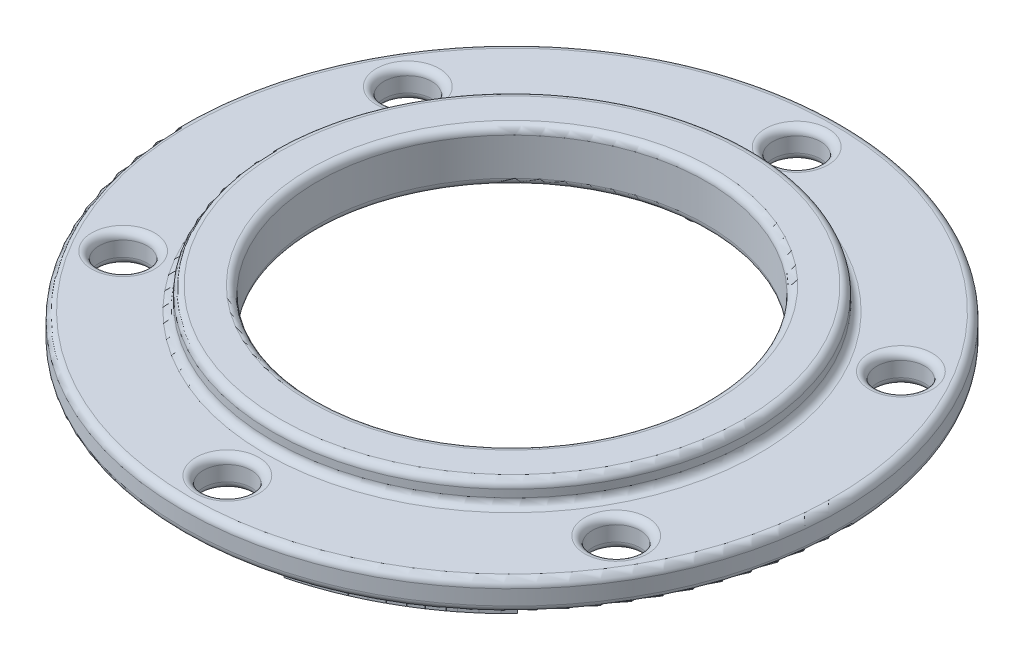
SolidWorks part; units mm, degrees
note: '?' marks a value the reader was unsure of.
other "graphite_1"
other "blue_5"
other "blue_8"
other "white_9"
other "white_3"
other "white_5"
other "white_10"
other "white_6"
other "white_2"
other "white_7"
other "white_8"
other "white"
other "white_4"
other "blue_6"
other "blue_4"
other "blue_2"
other "blue_1"
other "blue_3"
other "blue_7"
ref_plane "Front Plane" through (0, 0, 0) normal (0, 0, 1) x (1, 0, 0)
ref_plane "Top Plane" through (0, 0, 0) normal (0, 1, 0) x (1, 0, 0)
ref_plane "Right Plane" through (0, 0, 0) normal (1, 0, 0) x (0, 0, -1)
sketch "Sketch1" plane through (0, 0, 0) normal (0, 1, 0) x (1, 0, 0)
  circle A0 centre (0, 0) radius 22.025
  arc A1 (-0.6528, -22.0153) -> (-0.6528, 22.0153) centre (0, 0) ccw construction
  circle A2 centre (0, 19.025) radius 1.6
  circle A3 centre (16.4761, 9.5125) radius 1.6
  circle A4 centre (16.4761, -9.5125) radius 1.6
  circle A5 centre (0, -19.025) radius 1.6
  circle A6 centre (-16.4761, -9.5125) radius 1.6
  circle A7 centre (-16.4761, 9.5125) radius 1.6
  circle A8 centre (0, 0) radius 13
  point P21 (0, 0)
  dimension "D1" = 3.2
  dimension "D3" = 26
  dimension "D4" = 44.05
  dimension "D2" = 6
extrude "Boss-Extrude1" add sketch "Sketch1" against normal blind 2
ref_axis "Axis1" through (0, -2.805, 0) along (0, 1, 0)?
sketch "Sketch2" plane through (0, 0, 0) normal (0, 1, 0) x (1, 0, 0)
  circle A0 centre (0, 0) radius 13
  circle A1 centre (0, 0) radius 16
  dimension "D1" = 26
  dimension "D2" = 32
extrude "Boss-Extrude2" add sketch "Sketch2" along normal blind 1.5
fillet "Fillet1" radius 0.5 18 edges at (0, 0, 22.025) (0, 0, -17.425) (16.4761, 0, -7.9125) (16.4761, 0, 11.1125) (0, 0, 20.625) (-16.4761, 0, 11.1125) (-16.4761, 0, -7.9125) (0, -2, 22.025) (0, -2, -17.425) (0, -2, 13) (16.4761, -2, -7.9125) (16.4761, -2, 11.1125) (0, -2, 20.625) (-16.4761, -2, 11.1125) (-16.4761, -2, -7.9125) (0, 0, 16) (0, 1.5, 13) (0, 1.5, 16)
sketch "GL_free_blue" plane through (0, 0, 0) normal (0, 1, 0) x (1, 0, 0)
  line L0 (9.3065, -18.9293) -> (8.4044, -19.3469)
  line L1 (8.4044, -19.3469) -> (7.0284, -16.9635)
  line L2 (7.0284, -16.9635) -> (7.8857, -16.4685)
  line L3 (7.8857, -16.4685) -> (9.3065, -18.9293)
  line L4 (10.1151, -18.5099) -> (8.0238, -14.8877)
  line L5 (8.0238, -14.8877) -> (8.8812, -14.3927)
  line L6 (8.8812, -14.3927) -> (10.9726, -18.015)
  line L7 (10.9726, -18.015) -> (10.1151, -18.5099)
  line L8 (10.3193, -15.0635) -> (11.1766, -14.5685)
  line L9 (11.1766, -14.5685) -> (12.5533, -16.953)
  line L10 (12.5533, -16.953) -> (11.7407, -17.5254)
  line L11 (11.7407, -17.5254) -> (10.3193, -15.0635)
  line L12 (-11.4547, -8.409) -> (-9.9656, -11.4327)
  line L13 (-9.9656, -11.4327) -> (-9.316, -14.6968)
  line L14 (-9.316, -14.6968) -> (-10.4966, -16.447)
  line L15 (-10.4966, -16.447) -> (-10.5417, -16.3435)
  line L16 (-10.5417, -16.3435) -> (-10.6348, -16.204)
  line L17 (-10.6348, -16.204) -> (-10.8207, -16.0356)
  line L18 (-10.8207, -16.0356) -> (-11.0474, -15.9284)
  line L19 (-11.0474, -15.9284) -> (-11.2118, -15.8957)
  line L20 (-11.2118, -15.8957) -> (-11.3172, -15.8933)
  line L21 (-11.3172, -15.8933) -> (-10.3675, -14.4853)
  line L22 (-10.3675, -14.4853) -> (-10.9112, -11.7534)
  line L23 (-10.9112, -11.7534) -> (-12.3304, -8.8719)
  line L24 (-12.3304, -8.8719) -> (-13.9598, -5.9918)
  line L25 (-13.9598, -5.9918) -> (-13.0981, -5.5043)
  line L26 (-13.0981, -5.5043) -> (-11.4547, -8.409)
  line L27 (19.1817, 0.2481) -> (19.145, 0.0001)
  line L28 (19.145, 0.0001) -> (19.1614, -0.1668)
  line L29 (19.1614, -0.1668) -> (19.2101, -0.3273)
  line L30 (19.2101, -0.3273) -> (19.3053, -0.495)
  line L31 (19.3053, -0.495) -> (17.577, -0.495)
  line L32 (17.577, -0.495) -> (15.272, -2.385)
  line L33 (15.272, -2.385) -> (14.5924, -4.2302)
  line L34 (14.5924, -4.2302) -> (13.4188, -7.1349)
  line L35 (13.4188, -7.1349) -> (11.6421, -9.7689)
  line L36 (11.6421, -9.7689) -> (9.8494, -11.5002)
  line L37 (9.8494, -11.5002) -> (9.794, -11.2758)
  line L38 (9.794, -11.2758) -> (9.7196, -11.1365)
  line L39 (9.7196, -11.1365) -> (9.6194, -11.0144)
  line L40 (9.6194, -11.0144) -> (9.4298, -10.8738)
  line L41 (9.4298, -10.8738) -> (9.2839, -10.8134)
  line L42 (9.2839, -10.8134) -> (9.1617, -10.788)
  line L43 (9.1617, -10.788) -> (10.8796, -9.129)
  line L44 (10.8796, -9.129) -> (12.5399, -6.6676)
  line L45 (12.5399, -6.6676) -> (13.6687, -3.8736)
  line L46 (13.6687, -3.8736) -> (14.4361, -1.7902)
  line L47 (14.4361, -1.7902) -> (17.223, 0.495)
  line L48 (17.223, 0.495) -> (19.3047, 0.495)
  line L49 (19.3047, 0.495) -> (19.2459, 0.403)
  line L50 (19.2459, 0.403) -> (19.1817, 0.2481)
  line L51 (-17.6255, 0.445) -> (-17.105, 0.445)
  line L52 (-17.105, 0.445) -> (-17.105, -0.445)
  line L53 (-17.105, -0.445) -> (-17.6255, -0.445)
  line L54 (-17.6255, -0.445) -> (-17.6255, -1.4051)
  line L55 (-17.6255, -1.4051) -> (-17.0578, -1.3454)
  line L56 (-17.0578, -1.3454) -> (-16.9648, -2.2305)
  line L57 (-16.9648, -2.2305) -> (-17.6255, -2.3)
  line L58 (-17.6255, -2.3) -> (-17.6255, -3.1586)
  line L59 (-17.6255, -3.1586) -> (-17.3907, -4.7392)
  line L60 (-17.3907, -4.7392) -> (-17.4793, -4.6944)
  line L61 (-17.4793, -4.6944) -> (-17.6302, -4.6486)
  line L62 (-17.6302, -4.6486) -> (-17.7873, -4.6331)
  line L63 (-17.7873, -4.6331) -> (-17.9444, -4.6486)
  line L64 (-17.9444, -4.6486) -> (-18.1667, -4.7281)
  line L65 (-18.1667, -4.7281) -> (-18.2979, -4.8158)
  line L66 (-18.2979, -4.8158) -> (-18.3699, -4.8847)
  line L67 (-18.3699, -4.8847) -> (-18.6155, -3.2317)
  line L68 (-18.6155, -3.2317) -> (-18.6155, -2.404)
  line L69 (-18.6155, -2.404) -> (-19.5406, -2.5013)
  line L70 (-19.5406, -2.5013) -> (-19.6336, -1.6161)
  line L71 (-19.6336, -1.6161) -> (-18.6155, -1.5091)
  line L72 (-18.6155, -1.5091) -> (-18.6155, -0.445)
  line L73 (-18.6155, -0.445) -> (-19.695, -0.445)
  line L74 (-19.695, -0.445) -> (-19.695, 0.445)
  line L75 (-19.695, 0.445) -> (-18.6155, 0.445)
  line L76 (-18.6155, 0.445) -> (-18.6155, 1.5091)
  line L77 (-18.6155, 1.5091) -> (-19.6336, 1.6161)
  line L78 (-19.6336, 1.6161) -> (-19.5406, 2.5013)
  line L79 (-19.5406, 2.5013) -> (-18.6155, 2.404)
  line L80 (-18.6155, 2.404) -> (-18.6155, 3.2317)
  line L81 (-18.6155, 3.2317) -> (-18.3699, 4.8847)
  line L82 (-18.3699, 4.8847) -> (-18.2979, 4.8158)
  line L83 (-18.2979, 4.8158) -> (-18.1667, 4.7281)
  line L84 (-18.1667, 4.7281) -> (-17.9444, 4.6486)
  line L85 (-17.9444, 4.6486) -> (-17.7873, 4.6331)
  line L86 (-17.7873, 4.6331) -> (-17.6302, 4.6486)
  line L87 (-17.6302, 4.6486) -> (-17.4793, 4.6944)
  line L88 (-17.4793, 4.6944) -> (-17.3907, 4.7392)
  line L89 (-17.3907, 4.7392) -> (-17.6255, 3.1586)
  line L90 (-17.6255, 3.1586) -> (-17.6255, 2.3)
  line L91 (-17.6255, 2.3) -> (-16.9648, 2.2305)
  line L92 (-16.9648, 2.2305) -> (-17.0578, 1.3454)
  line L93 (-17.0578, 1.3454) -> (-17.6255, 1.4051)
  line L94 (-17.6255, 1.4051) -> (-17.6255, 0.445)
  line L95 (-2.8163, 14.7905) -> (-2.8509, 14.5569)
  line L96 (-2.8509, 14.5569) -> (-2.8162, 14.3232)
  line L97 (-2.8162, 14.3232) -> (-2.7153, 14.1098)
  line L98 (-2.7153, 14.1098) -> (-2.6151, 13.9877)
  line L99 (-2.6151, 13.9877) -> (-2.5403, 13.9235)
  line L100 (-2.5403, 13.9235) -> (-4.9445, 13.3241)
  line L101 (-4.9445, 13.3241) -> (-6.7566, 13.1559)
  line L102 (-6.7566, 13.1559) -> (-9.208, 14.3636)
  line L103 (-9.208, 14.3636) -> (-10.1607, 15.9492)
  line L104 (-10.1607, 15.9492) -> (-10.0109, 15.9496)
  line L105 (-10.0109, 15.9496) -> (-9.8464, 15.9823)
  line L106 (-9.8464, 15.9823) -> (-9.6197, 16.0895)
  line L107 (-9.6197, 16.0895) -> (-9.4338, 16.258)
  line L108 (-9.4338, 16.258) -> (-9.3123, 16.4594)
  line L109 (-9.3123, 16.4594) -> (-8.5093, 15.123)
  line L110 (-8.5093, 15.123) -> (-6.5698, 14.1675)
  line L111 (-6.5698, 14.1675) -> (-5.1109, 14.3029)
  line L112 (-5.1109, 14.3029) -> (-2.7798, 14.8841)
  line L113 (-2.7798, 14.8841) -> (-2.8163, 14.7905)
  line L114 (10.8629, 13.5214) -> (10.6712, 13.512)
  line L115 (10.6712, 13.512) -> (10.5482, 13.4747)
  line L116 (10.5482, 13.4747) -> (10.4348, 13.4141)
  line L117 (10.4348, 13.4141) -> (10.2924, 13.2851)
  line L118 (10.2924, 13.2851) -> (10.1897, 13.1033)
  line L119 (10.1897, 13.1033) -> (9.5768, 14.8192)
  line L120 (9.5768, 14.8192) -> (9.4533, 16.4797)
  line L121 (9.4533, 16.4797) -> (9.6662, 16.377)
  line L122 (9.6662, 16.377) -> (9.8211, 16.3462)
  line L123 (9.8211, 16.3462) -> (9.979, 16.3462)
  line L124 (9.979, 16.3462) -> (10.208, 16.4035)
  line L125 (10.208, 16.4035) -> (10.3472, 16.4779)
  line L126 (10.3472, 16.4779) -> (10.4406, 16.5529)
  line L127 (10.4406, 16.5529) -> (10.5541, 15.0261)
  line L128 (10.5541, 15.0261) -> (11.1218, 13.4371)
  line L129 (11.1218, 13.4371) -> (10.989, 13.4964)
  line L130 (10.989, 13.4964) -> (10.8629, 13.5214)
extrude "GL_free_blue_raised" add sketch "GL_free_blue" along normal blind 0.6 from offset 2.6 separate body
sketch "GL_free_white" plane through (0, 0, 0) normal (0, 1, 0) x (1, 0, 0)
  line L0 (-10.6982, -17.344) -> (-10.8263, -17.4491)
  line L1 (-10.8263, -17.4491) -> (-10.9723, -17.5272)
  line L2 (-10.9723, -17.5272) -> (-11.1309, -17.5753)
  line L3 (-11.1309, -17.5753) -> (-11.2957, -17.5915)
  line L4 (-11.2957, -17.5915) -> (-11.4605, -17.5753)
  line L5 (-11.4605, -17.5753) -> (-11.6191, -17.5272)
  line L6 (-11.6191, -17.5272) -> (-11.7651, -17.4491)
  line L7 (-11.7651, -17.4491) -> (-11.8932, -17.344)
  line L8 (-11.8932, -17.344) -> (-11.9983, -17.216)
  line L9 (-11.9983, -17.216) -> (-12.0764, -17.0699)
  line L10 (-12.0764, -17.0699) -> (-12.1244, -16.9114)
  line L11 (-12.1244, -16.9114) -> (-12.1407, -16.7466)
  line L12 (-12.1407, -16.7466) -> (-12.1244, -16.5817)
  line L13 (-12.1244, -16.5817) -> (-12.0764, -16.4232)
  line L14 (-12.0764, -16.4232) -> (-11.9983, -16.2771)
  line L15 (-11.9983, -16.2771) -> (-11.8932, -16.1491)
  line L16 (-11.8932, -16.1491) -> (-11.7651, -16.044)
  line L17 (-11.7651, -16.044) -> (-11.6191, -15.9659)
  line L18 (-11.6191, -15.9659) -> (-11.4605, -15.9178)
  line L19 (-11.4605, -15.9178) -> (-11.2957, -15.9016)
  line L20 (-11.2957, -15.9016) -> (-11.1309, -15.9178)
  line L21 (-11.1309, -15.9178) -> (-10.9723, -15.9659)
  line L22 (-10.9723, -15.9659) -> (-10.8263, -16.044)
  line L23 (-10.8263, -16.044) -> (-10.6982, -16.1491)
  line L24 (-10.6982, -16.1491) -> (-10.5931, -16.2771)
  line L25 (-10.5931, -16.2771) -> (-10.515, -16.4232)
  line L26 (-10.515, -16.4232) -> (-10.467, -16.5817)
  line L27 (-10.467, -16.5817) -> (-10.4507, -16.7466)
  line L28 (-10.4507, -16.7466) -> (-10.467, -16.9114)
  line L29 (-10.467, -16.9114) -> (-10.515, -17.0699)
  line L30 (-10.515, -17.0699) -> (-10.5931, -17.216)
  line L31 (-10.5931, -17.216) -> (-10.6982, -17.344)
  line L32 (11.7323, -17.531) -> (10.9811, -18.0098)
  line L33 (10.9811, -18.0098) -> (8.8848, -14.379)
  line L34 (8.8848, -14.379) -> (8.0102, -14.884)
  line L35 (8.0102, -14.884) -> (10.1063, -18.5147)
  line L36 (10.1063, -18.5147) -> (9.3155, -18.9249)
  line L37 (9.3155, -18.9249) -> (7.8894, -16.4548)
  line L38 (7.8894, -16.4548) -> (7.0147, -16.9598)
  line L39 (7.0147, -16.9598) -> (8.3952, -19.3509)
  line L40 (8.3952, -19.3509) -> (7.592, -19.6815)
  line L41 (7.592, -19.6815) -> (6.6171, -20.0303)
  line L42 (6.6171, -20.0303) -> (6.1236, -20.1866)
  line L43 (6.1236, -20.1866) -> (5.2036, -20.4422)
  line L44 (5.2036, -20.4422) -> (4.4572, -16.6159)
  line L45 (4.4572, -16.6159) -> (7.9525, -13.7742)
  line L46 (7.9525, -13.7742) -> (12.1612, -12.168)
  line L47 (12.1612, -12.168) -> (15.1011, -14.727)
  line L48 (15.1011, -14.727) -> (14.5459, -15.278)
  line L49 (14.5459, -15.278) -> (13.7787, -15.9733)
  line L50 (13.7787, -15.9733) -> (12.9783, -16.6302)
  line L51 (12.9783, -16.6302) -> (12.5614, -16.947)
  line L52 (12.5614, -16.947) -> (11.1803, -14.5548)
  line L53 (11.1803, -14.5548) -> (10.3056, -15.0598)
  line L54 (10.3056, -15.0598) -> (11.7323, -17.531)
  line L55 (9.6124, -12.1459) -> (9.4919, -12.2448)
  line L56 (9.4919, -12.2448) -> (9.3544, -12.3182)
  line L57 (9.3544, -12.3182) -> (9.2053, -12.3635)
  line L58 (9.2053, -12.3635) -> (9.0502, -12.3787)
  line L59 (9.0502, -12.3787) -> (8.8951, -12.3635)
  line L60 (8.8951, -12.3635) -> (8.746, -12.3182)
  line L61 (8.746, -12.3182) -> (8.6086, -12.2448)
  line L62 (8.6086, -12.2448) -> (8.4881, -12.1459)
  line L63 (8.4881, -12.1459) -> (8.3892, -12.0254)
  line L64 (8.3892, -12.0254) -> (8.3158, -11.888)
  line L65 (8.3158, -11.888) -> (8.2705, -11.7389)
  line L66 (8.2705, -11.7389) -> (8.2552, -11.5838)
  line L67 (8.2552, -11.5838) -> (8.2705, -11.4287)
  line L68 (8.2705, -11.4287) -> (8.3158, -11.2795)
  line L69 (8.3158, -11.2795) -> (8.3892, -11.1421)
  line L70 (8.3892, -11.1421) -> (8.4881, -11.0216)
  line L71 (8.4881, -11.0216) -> (8.6086, -10.9228)
  line L72 (8.6086, -10.9228) -> (8.746, -10.8493)
  line L73 (8.746, -10.8493) -> (8.8951, -10.8041)
  line L74 (8.8951, -10.8041) -> (9.0502, -10.7888)
  line L75 (9.0502, -10.7888) -> (9.2053, -10.8041)
  line L76 (9.2053, -10.8041) -> (9.3544, -10.8493)
  line L77 (9.3544, -10.8493) -> (9.4919, -10.9228)
  line L78 (9.4919, -10.9228) -> (9.6124, -11.0216)
  line L79 (9.6124, -11.0216) -> (9.7112, -11.1421)
  line L80 (9.7112, -11.1421) -> (9.7847, -11.2795)
  line L81 (9.7847, -11.2795) -> (9.8299, -11.4287)
  line L82 (9.8299, -11.4287) -> (9.8452, -11.5838)
  line L83 (9.8452, -11.5838) -> (9.8299, -11.7389)
  line L84 (9.8299, -11.7389) -> (9.7847, -11.888)
  line L85 (9.7847, -11.888) -> (9.7112, -12.0254)
  line L86 (9.7112, -12.0254) -> (9.6124, -12.1459)
  line L87 (-17.3456, -6.0991) -> (-17.483, -6.1726)
  line L88 (-17.483, -6.1726) -> (-17.6322, -6.2178)
  line L89 (-17.6322, -6.2178) -> (-17.7873, -6.2331)
  line L90 (-17.7873, -6.2331) -> (-17.9424, -6.2178)
  line L91 (-17.9424, -6.2178) -> (-18.0915, -6.1726)
  line L92 (-18.0915, -6.1726) -> (-18.2289, -6.0991)
  line L93 (-18.2289, -6.0991) -> (-18.3494, -6.0002)
  line L94 (-18.3494, -6.0002) -> (-18.4483, -5.8798)
  line L95 (-18.4483, -5.8798) -> (-18.5217, -5.7423)
  line L96 (-18.5217, -5.7423) -> (-18.567, -5.5932)
  line L97 (-18.567, -5.5932) -> (-18.5822, -5.4381)
  line L98 (-18.5822, -5.4381) -> (-18.567, -5.283)
  line L99 (-18.567, -5.283) -> (-18.5217, -5.1339)
  line L100 (-18.5217, -5.1339) -> (-18.4483, -4.9964)
  line L101 (-18.4483, -4.9964) -> (-18.3494, -4.876)
  line L102 (-18.3494, -4.876) -> (-18.2289, -4.7771)
  line L103 (-18.2289, -4.7771) -> (-18.0915, -4.7037)
  line L104 (-18.0915, -4.7037) -> (-17.9424, -4.6584)
  line L105 (-17.9424, -4.6584) -> (-17.7873, -4.6431)
  line L106 (-17.7873, -4.6431) -> (-17.6322, -4.6584)
  line L107 (-17.6322, -4.6584) -> (-17.483, -4.7037)
  line L108 (-17.483, -4.7037) -> (-17.3456, -4.7771)
  line L109 (-17.3456, -4.7771) -> (-17.2251, -4.876)
  line L110 (-17.2251, -4.876) -> (-17.1263, -4.9964)
  line L111 (-17.1263, -4.9964) -> (-17.0528, -5.1339)
  line L112 (-17.0528, -5.1339) -> (-17.0076, -5.283)
  line L113 (-17.0076, -5.283) -> (-16.9923, -5.4381)
  line L114 (-16.9923, -5.4381) -> (-17.0076, -5.5932)
  line L115 (-17.0076, -5.5932) -> (-17.0528, -5.7423)
  line L116 (-17.0528, -5.7423) -> (-17.1263, -5.8798)
  line L117 (-17.1263, -5.8798) -> (-17.2251, -6.0002)
  line L118 (-17.2251, -6.0002) -> (-17.3456, -6.0991)
  line L119 (20.4694, -0.7026) -> (20.3234, -0.7807)
  line L120 (20.3234, -0.7807) -> (20.1648, -0.8287)
  line L121 (20.1648, -0.8287) -> (20, -0.845)
  line L122 (20, -0.845) -> (19.8352, -0.8287)
  line L123 (19.8352, -0.8287) -> (19.6766, -0.7807)
  line L124 (19.6766, -0.7807) -> (19.5306, -0.7026)
  line L125 (19.5306, -0.7026) -> (19.4025, -0.5975)
  line L126 (19.4025, -0.5975) -> (19.2974, -0.4694)
  line L127 (19.2974, -0.4694) -> (19.2193, -0.3234)
  line L128 (19.2193, -0.3234) -> (19.1713, -0.1648)
  line L129 (19.1713, -0.1648) -> (19.155, 0)
  line L130 (19.155, 0) -> (19.1713, 0.1648)
  line L131 (19.1713, 0.1648) -> (19.2193, 0.3234)
  line L132 (19.2193, 0.3234) -> (19.2974, 0.4694)
  line L133 (19.2974, 0.4694) -> (19.4025, 0.5975)
  line L134 (19.4025, 0.5975) -> (19.5306, 0.7026)
  line L135 (19.5306, 0.7026) -> (19.6766, 0.7807)
  line L136 (19.6766, 0.7807) -> (19.8352, 0.8287)
  line L137 (19.8352, 0.8287) -> (20, 0.845)
  line L138 (20, 0.845) -> (20.1648, 0.8287)
  line L139 (20.1648, 0.8287) -> (20.3234, 0.7807)
  line L140 (20.3234, 0.7807) -> (20.4694, 0.7026)
  line L141 (20.4694, 0.7026) -> (20.5975, 0.5975)
  line L142 (20.5975, 0.5975) -> (20.7026, 0.4694)
  line L143 (20.7026, 0.4694) -> (20.7807, 0.3234)
  line L144 (20.7807, 0.3234) -> (20.8287, 0.1648)
  line L145 (20.8287, 0.1648) -> (20.845, 0)
  line L146 (20.845, 0) -> (20.8287, -0.1648)
  line L147 (20.8287, -0.1648) -> (20.7807, -0.3234)
  line L148 (20.7807, -0.3234) -> (20.7026, -0.4694)
  line L149 (20.7026, -0.4694) -> (20.5975, -0.5975)
  line L150 (20.5975, -0.5975) -> (20.4694, -0.7026)
  line L151 (-17.2251, 4.876) -> (-17.3456, 4.7771)
  line L152 (-17.3456, 4.7771) -> (-17.483, 4.7037)
  line L153 (-17.483, 4.7037) -> (-17.6322, 4.6584)
  line L154 (-17.6322, 4.6584) -> (-17.7873, 4.6431)
  line L155 (-17.7873, 4.6431) -> (-17.9424, 4.6584)
  line L156 (-17.9424, 4.6584) -> (-18.0915, 4.7037)
  line L157 (-18.0915, 4.7037) -> (-18.2289, 4.7771)
  line L158 (-18.2289, 4.7771) -> (-18.3494, 4.876)
  line L159 (-18.3494, 4.876) -> (-18.4483, 4.9964)
  line L160 (-18.4483, 4.9964) -> (-18.5217, 5.1339)
  line L161 (-18.5217, 5.1339) -> (-18.567, 5.283)
  line L162 (-18.567, 5.283) -> (-18.5822, 5.4381)
  line L163 (-18.5822, 5.4381) -> (-18.567, 5.5932)
  line L164 (-18.567, 5.5932) -> (-18.5217, 5.7423)
  line L165 (-18.5217, 5.7423) -> (-18.4483, 5.8798)
  line L166 (-18.4483, 5.8798) -> (-18.3494, 6.0002)
  line L167 (-18.3494, 6.0002) -> (-18.2289, 6.0991)
  line L168 (-18.2289, 6.0991) -> (-18.0915, 6.1726)
  line L169 (-18.0915, 6.1726) -> (-17.9424, 6.2178)
  line L170 (-17.9424, 6.2178) -> (-17.7873, 6.2331)
  line L171 (-17.7873, 6.2331) -> (-17.6322, 6.2178)
  line L172 (-17.6322, 6.2178) -> (-17.483, 6.1726)
  line L173 (-17.483, 6.1726) -> (-17.3456, 6.0991)
  line L174 (-17.3456, 6.0991) -> (-17.2251, 6.0002)
  line L175 (-17.2251, 6.0002) -> (-17.1263, 5.8798)
  line L176 (-17.1263, 5.8798) -> (-17.0528, 5.7423)
  line L177 (-17.0528, 5.7423) -> (-17.0076, 5.5932)
  line L178 (-17.0076, 5.5932) -> (-16.9923, 5.4381)
  line L179 (-16.9923, 5.4381) -> (-17.0076, 5.283)
  line L180 (-17.0076, 5.283) -> (-17.0528, 5.1339)
  line L181 (-17.0528, 5.1339) -> (-17.1263, 4.9964)
  line L182 (-17.1263, 4.9964) -> (-17.2251, 4.876)
  line L183 (11.2549, 12.4135) -> (11.1572, 12.3333)
  line L184 (11.1572, 12.3333) -> (11.0457, 12.2737)
  line L185 (11.0457, 12.2737) -> (10.9247, 12.237)
  line L186 (10.9247, 12.237) -> (10.7988, 12.2246)
  line L187 (10.7988, 12.2246) -> (10.673, 12.237)
  line L188 (10.673, 12.237) -> (10.552, 12.2737)
  line L189 (10.552, 12.2737) -> (10.4405, 12.3333)
  line L190 (10.4405, 12.3333) -> (10.3428, 12.4135)
  line L191 (10.3428, 12.4135) -> (10.2626, 12.5112)
  line L192 (10.2626, 12.5112) -> (10.203, 12.6227)
  line L193 (10.203, 12.6227) -> (10.1662, 12.7437)
  line L194 (10.1662, 12.7437) -> (10.1539, 12.8695)
  line L195 (10.1539, 12.8695) -> (10.1662, 12.9954)
  line L196 (10.1662, 12.9954) -> (10.203, 13.1164)
  line L197 (10.203, 13.1164) -> (10.2626, 13.2279)
  line L198 (10.2626, 13.2279) -> (10.3428, 13.3256)
  line L199 (10.3428, 13.3256) -> (10.4405, 13.4058)
  line L200 (10.4405, 13.4058) -> (10.552, 13.4654)
  line L201 (10.552, 13.4654) -> (10.673, 13.5021)
  line L202 (10.673, 13.5021) -> (10.7988, 13.5145)
  line L203 (10.7988, 13.5145) -> (10.9247, 13.5021)
  line L204 (10.9247, 13.5021) -> (11.0457, 13.4654)
  line L205 (11.0457, 13.4654) -> (11.1572, 13.4058)
  line L206 (11.1572, 13.4058) -> (11.2549, 13.3256)
  line L207 (11.2549, 13.3256) -> (11.3351, 13.2279)
  line L208 (11.3351, 13.2279) -> (11.3947, 13.1164)
  line L209 (11.3947, 13.1164) -> (11.4314, 12.9954)
  line L210 (11.4314, 12.9954) -> (11.4438, 12.8695)
  line L211 (11.4438, 12.8695) -> (11.4314, 12.7437)
  line L212 (11.4314, 12.7437) -> (11.3947, 12.6227)
  line L213 (11.3947, 12.6227) -> (11.3351, 12.5112)
  line L214 (11.3351, 12.5112) -> (11.2549, 12.4135)
  line L215 (-1.4837, 13.9948) -> (-1.6042, 13.8959)
  line L216 (-1.6042, 13.8959) -> (-1.7416, 13.8225)
  line L217 (-1.7416, 13.8225) -> (-1.8908, 13.7772)
  line L218 (-1.8908, 13.7772) -> (-2.0458, 13.762)
  line L219 (-2.0458, 13.762) -> (-2.2009, 13.7772)
  line L220 (-2.2009, 13.7772) -> (-2.3501, 13.8225)
  line L221 (-2.3501, 13.8225) -> (-2.4875, 13.8959)
  line L222 (-2.4875, 13.8959) -> (-2.608, 13.9948)
  line L223 (-2.608, 13.9948) -> (-2.7068, 14.1153)
  line L224 (-2.7068, 14.1153) -> (-2.7803, 14.2527)
  line L225 (-2.7803, 14.2527) -> (-2.8255, 14.4018)
  line L226 (-2.8255, 14.4018) -> (-2.8408, 14.5569)
  line L227 (-2.8408, 14.5569) -> (-2.8255, 14.712)
  line L228 (-2.8255, 14.712) -> (-2.7803, 14.8612)
  line L229 (-2.7803, 14.8612) -> (-2.7068, 14.9986)
  line L230 (-2.7068, 14.9986) -> (-2.608, 15.1191)
  line L231 (-2.608, 15.1191) -> (-2.4875, 15.2179)
  line L232 (-2.4875, 15.2179) -> (-2.3501, 15.2914)
  line L233 (-2.3501, 15.2914) -> (-2.2009, 15.3366)
  line L234 (-2.2009, 15.3366) -> (-2.0458, 15.3519)
  line L235 (-2.0458, 15.3519) -> (-1.8908, 15.3366)
  line L236 (-1.8908, 15.3366) -> (-1.7416, 15.2914)
  line L237 (-1.7416, 15.2914) -> (-1.6042, 15.2179)
  line L238 (-1.6042, 15.2179) -> (-1.4837, 15.1191)
  line L239 (-1.4837, 15.1191) -> (-1.3848, 14.9986)
  line L240 (-1.3848, 14.9986) -> (-1.3114, 14.8612)
  line L241 (-1.3114, 14.8612) -> (-1.2661, 14.712)
  line L242 (-1.2661, 14.712) -> (-1.2509, 14.5569)
  line L243 (-1.2509, 14.5569) -> (-1.2661, 14.4018)
  line L244 (-1.2661, 14.4018) -> (-1.3114, 14.2527)
  line L245 (-1.3114, 14.2527) -> (-1.3848, 14.1153)
  line L246 (-1.3848, 14.1153) -> (-1.4837, 13.9948)
  line L247 (-9.6253, 16.0979) -> (-9.7714, 16.0198)
  line L248 (-9.7714, 16.0198) -> (-9.9299, 15.9717)
  line L249 (-9.9299, 15.9717) -> (-10.0947, 15.9555)
  line L250 (-10.0947, 15.9555) -> (-10.2596, 15.9717)
  line L251 (-10.2596, 15.9717) -> (-10.4181, 16.0198)
  line L252 (-10.4181, 16.0198) -> (-10.5642, 16.0979)
  line L253 (-10.5642, 16.0979) -> (-10.6922, 16.203)
  line L254 (-10.6922, 16.203) -> (-10.7973, 16.331)
  line L255 (-10.7973, 16.331) -> (-10.8754, 16.4771)
  line L256 (-10.8754, 16.4771) -> (-10.9235, 16.6356)
  line L257 (-10.9235, 16.6356) -> (-10.9397, 16.8005)
  line L258 (-10.9397, 16.8005) -> (-10.9235, 16.9653)
  line L259 (-10.9235, 16.9653) -> (-10.8754, 17.1238)
  line L260 (-10.8754, 17.1238) -> (-10.7973, 17.2699)
  line L261 (-10.7973, 17.2699) -> (-10.6922, 17.398)
  line L262 (-10.6922, 17.398) -> (-10.5642, 17.5031)
  line L263 (-10.5642, 17.5031) -> (-10.4181, 17.5811)
  line L264 (-10.4181, 17.5811) -> (-10.2596, 17.6292)
  line L265 (-10.2596, 17.6292) -> (-10.0947, 17.6455)
  line L266 (-10.0947, 17.6455) -> (-9.9299, 17.6292)
  line L267 (-9.9299, 17.6292) -> (-9.7714, 17.5811)
  line L268 (-9.7714, 17.5811) -> (-9.6253, 17.5031)
  line L269 (-9.6253, 17.5031) -> (-9.4973, 17.398)
  line L270 (-9.4973, 17.398) -> (-9.3922, 17.2699)
  line L271 (-9.3922, 17.2699) -> (-9.3141, 17.1238)
  line L272 (-9.3141, 17.1238) -> (-9.266, 16.9653)
  line L273 (-9.266, 16.9653) -> (-9.2498, 16.8005)
  line L274 (-9.2498, 16.8005) -> (-9.266, 16.6356)
  line L275 (-9.266, 16.6356) -> (-9.3141, 16.4771)
  line L276 (-9.3141, 16.4771) -> (-9.3922, 16.331)
  line L277 (-9.3922, 16.331) -> (-9.4973, 16.203)
  line L278 (-9.4973, 16.203) -> (-9.6253, 16.0979)
  line L279 (10.3417, 16.4863) -> (10.2042, 16.4128)
  line L280 (10.2042, 16.4128) -> (10.0551, 16.3676)
  line L281 (10.0551, 16.3676) -> (9.9, 16.3523)
  line L282 (9.9, 16.3523) -> (9.7449, 16.3676)
  line L283 (9.7449, 16.3676) -> (9.5958, 16.4128)
  line L284 (9.5958, 16.4128) -> (9.4583, 16.4863)
  line L285 (9.4583, 16.4863) -> (9.3379, 16.5852)
  line L286 (9.3379, 16.5852) -> (9.239, 16.7056)
  line L287 (9.239, 16.7056) -> (9.1655, 16.8431)
  line L288 (9.1655, 16.8431) -> (9.1203, 16.9922)
  line L289 (9.1203, 16.9922) -> (9.105, 17.1473)
  line L290 (9.105, 17.1473) -> (9.1203, 17.3024)
  line L291 (9.1203, 17.3024) -> (9.1655, 17.4515)
  line L292 (9.1655, 17.4515) -> (9.239, 17.589)
  line L293 (9.239, 17.589) -> (9.3379, 17.7094)
  line L294 (9.3379, 17.7094) -> (9.4583, 17.8083)
  line L295 (9.4583, 17.8083) -> (9.5958, 17.8818)
  line L296 (9.5958, 17.8818) -> (9.7449, 17.927)
  line L297 (9.7449, 17.927) -> (9.9, 17.9423)
  line L298 (9.9, 17.9423) -> (10.0551, 17.927)
  line L299 (10.0551, 17.927) -> (10.2042, 17.8818)
  line L300 (10.2042, 17.8818) -> (10.3417, 17.8083)
  line L301 (10.3417, 17.8083) -> (10.4621, 17.7094)
  line L302 (10.4621, 17.7094) -> (10.561, 17.589)
  line L303 (10.561, 17.589) -> (10.6345, 17.4515)
  line L304 (10.6345, 17.4515) -> (10.6797, 17.3024)
  line L305 (10.6797, 17.3024) -> (10.695, 17.1473)
  line L306 (10.695, 17.1473) -> (10.6797, 16.9922)
  line L307 (10.6797, 16.9922) -> (10.6345, 16.8431)
  line L308 (10.6345, 16.8431) -> (10.561, 16.7056)
  line L309 (10.561, 16.7056) -> (10.4621, 16.5852)
  line L310 (10.4621, 16.5852) -> (10.3417, 16.4863)
extrude "GL_free_white_raised" add sketch "GL_free_white" along normal blind 0.6 from offset 2.6 separate body
